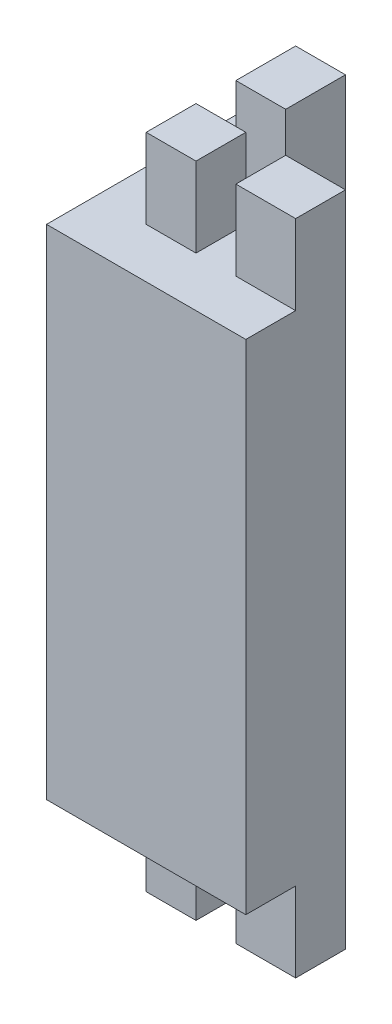
SolidWorks part; units mm, degrees
ref_plane "Front Plane" through (0, 0, 0) normal (0, 0, 1) x (1, 0, 0)
ref_plane "Top Plane" through (0, 0, 0) normal (0, 1, 0) x (1, 0, 0)
ref_plane "Right Plane" through (0, 0, 0) normal (1, 0, 0) x (0, 0, -1)
sketch "Sketch12" plane through (0, 0, 0) normal (0, 1, 0) x (1, 0, 0)
  line L0 (-5, -5) -> (5, -5)
  line L1 (-5, -5) -> (-5, 0)
  line L2 (0, 0) -> (5, 0)
  line L3 (5, -5) -> (5, 0)
  line L4 (-5, 0) -> (-5, 5)
  line L5 (-5, 5) -> (0, 5)
  line L6 (0, 0) -> (0, 5)
  dimension "D1" = 5
  dimension "D2" = 10
  dimension "D3" = 5
  dimension "D4" = 5
extrude "Boss-Extrude2" add sketch "Sketch12" along normal blind 25
sketch "Sketch13" plane through (0, 0, 0) normal (0, 1, 0) x (1, 0, 0)
  line L1 (0, 5) -> (-2.5, 5)
  line L2 (0, 5) -> (0, 2)
  line L3 (0, 2) -> (-2.5, 2)
  line L4 (-2.5, 5) -> (-2.5, 2)
  line L5 (5, 0) -> (2, 0)
  line L6 (5, 0) -> (5, -2.5)
  line L7 (5, -2.5) -> (2, -2.5)
  line L8 (2, 0) -> (2, -2.5)
  line L9 (0, 0) -> (-2.5, 0)
  line L10 (0, 0) -> (0, -2.5)
  line L11 (0, -2.5) -> (-2.5, -2.5)
  line L12 (-2.5, 0) -> (-2.5, -2.5)
  dimension "D1" = 2.5
  dimension "D2" = 3
  dimension "D3" = 3
  dimension "D4" = 2.5
extrude "Boss-Extrude3" add sketch "Sketch13" against normal blind 4
sketch "Sketch15" plane through (0, 25, 0) normal (0, 1, 0) x (1, 0, 0)
  line L0 (5, 0) -> (0, 0) construction
  line L1 (0, 5) -> (-2.5, 5)
  line L2 (0, 5) -> (0, 2)
  line L3 (0, 2) -> (-2.5, 2)
  line L4 (-2.5, 5) -> (-2.5, 2)
  line L5 (5, 0) -> (2, 0)
  line L6 (5, 0) -> (5, -2.5)
  line L7 (5, -2.5) -> (2, -2.5)
  line L8 (2, 0) -> (2, -2.5)
  line L9 (0, 0) -> (-2.5, 0)
  line L10 (0, 0) -> (0, -2.5)
  line L11 (0, -2.5) -> (-2.5, -2.5)
  line L12 (-2.5, 0) -> (-2.5, -2.5)
  line L13 (5, -5) -> (5, 0) construction
  dimension "D1" = 2.5
  dimension "D2" = 3
  dimension "D3" = 3
  dimension "D4" = 2.5
  dimension "D5" = 2.5
  dimension "D6" = 2.5
  dimension "D7" = 2
  dimension "D8" = 2
  dimension "D9" = 7.5
extrude "Boss-Extrude4" add sketch "Sketch15" along normal blind 4
